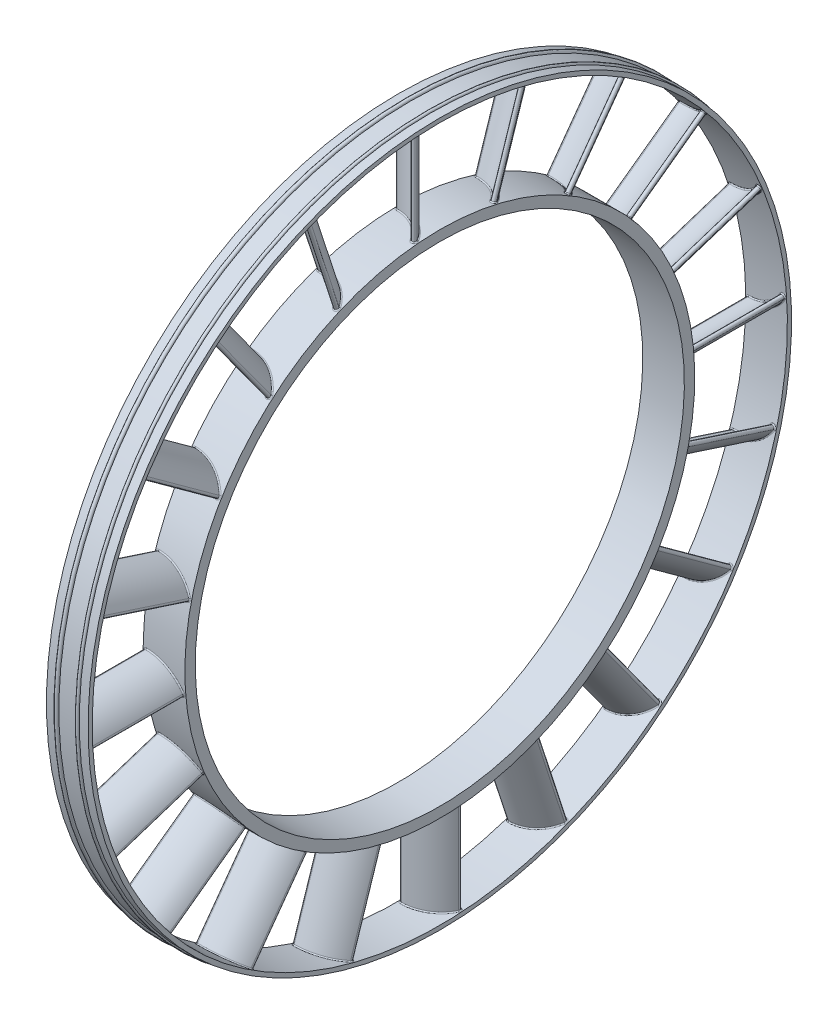
SolidWorks part; units mm, degrees
ref_plane "Front Plane" through (0, 0, 0) normal (0, 0, 1) x (1, 0, 0)
ref_plane "Top Plane" through (0, 0, 0) normal (0, 1, 0) x (1, 0, 0)
ref_plane "Right Plane" through (0, 0, 0) normal (1, 0, 0) x (0, 0, -1)
sketch "Sketch1" plane through (0, 0, 0) normal (0, 0, 1) x (1, 0, 0)
  line L0 (75.603, 0) -> (-75.603, 0) construction
  line L1 (-10, 117.5) -> (-10, 122.5)
  line L2 (10, 117.5) -> (-10, 117.5)
  line L3 (-10, 122.5) -> (10, 122.5)
  line L4 (10, 122.5) -> (10, 117.5)
  line L5 (-10, 169) -> (-10, 167)
  line L6 (-10, 169) -> (-5.98, 169)
  line L7 (-10, 167) -> (10, 167)
  line L8 (10, 167) -> (10, 169)
  line L9 (-4.02, 169) -> (4.22, 169)
  line L10 (5.78, 169) -> (10, 169)
  arc A0 (-4.02, 169) -> (-5.98, 169) centre (-5, 169) ccw
  arc A1 (5.78, 169) -> (4.22, 169) centre (5, 169) ccw
  point P4 (0, 0)
  point P10 (0, 117.5)
  dimension "D8" = 5
  dimension "D1" = 2
  dimension "D2" = 20
  dimension "D3" = 167
  dimension "D4" = 117.5
  dimension "D5" = 5
  dimension "D6" = 20
  dimension "D9" = 5
revolve "Revolve1" add sketch "Sketch1" angle 360 about L0
sketch "Sketch2" plane through (0, 0, 0) normal (0, 1, 0) x (1, 0, 0)
  line L0 (-10, 169) -> (-10, -169) construction
  line L1 (10, -169) -> (10, 169) construction
  arc A0 (-8.5, 0) -> (9, -10) centre (-8.321, -19.9992) cw
  arc A1 (-8.4821, -1.9999) -> (7.2679, -10.9999) centre (-8.321, -19.9992) cw
  arc A2 (-8.5, 0) -> (-8.4821, -1.9999) centre (-8.491, -1) ccw
  arc A3 (7.2679, -10.9999) -> (9, -10) centre (8.134, -10.5) ccw
  dimension "D3" = 20
  dimension "D1" = 1.5
  dimension "D2" = 1
  dimension "D4" = 10
  dimension "D5" = 2
extrude "Boss-Extrude1" add sketch "Sketch2" along normal up to surface (48.2003 mm away) from offset 118.5
fillet "Fillet1" radius 0.5 8 edges at (8.6715, 121.9737, 11.3432) (-3.9752, 122.4738, 2.5317) (-9.4667, 122.4975, 0.7804) (-9.4853, 166.9976, 0.8931) (-1.7382, 166.9684, 3.2461) (8.5276, 166.6091, 11.4192) (-0.971, 122.492, 1.3987) (4.0313, 166.9454, 4.2695)
pattern_circular "CirPattern1" count 20 over 360 about axis through (10, 0, 0) along (1, 0, 0) of "Boss-Extrude1", "Fillet1"
